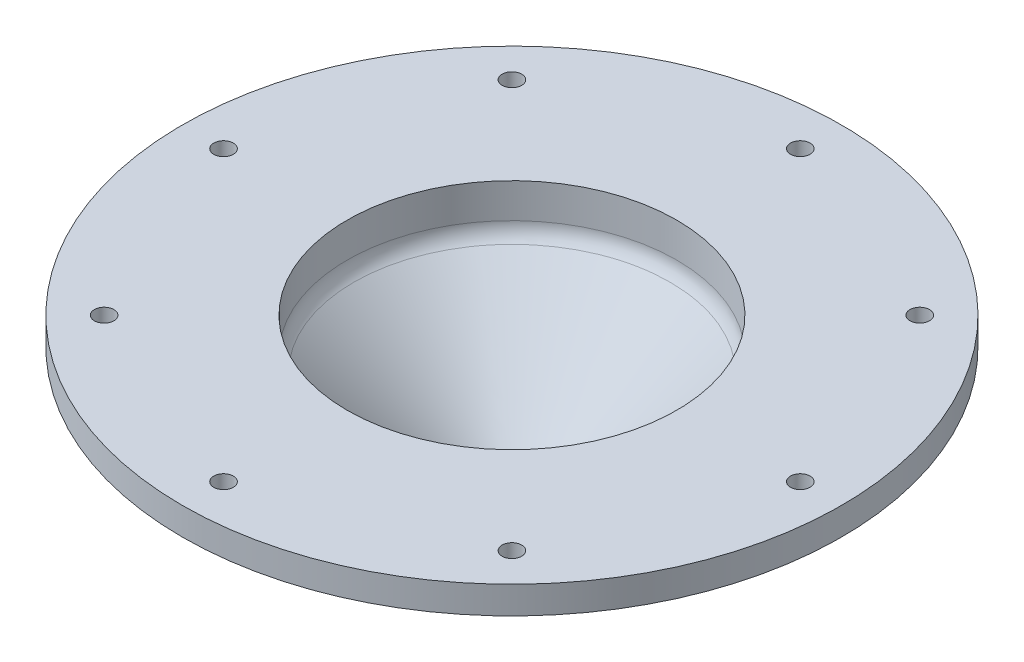
SolidWorks part; units mm, degrees
material "7075-T6 (SN)"
ref_plane "Front Plane" through (0, 0, 0) normal (0, 0, 1) x (1, 0, 0)
ref_plane "Top Plane" through (0, 0, 0) normal (0, 1, 0) x (1, 0, 0)
ref_plane "Right Plane" through (0, 0, 0) normal (1, 0, 0) x (0, 0, -1)
sketch "Sketch1" plane through (0, 0, 0) normal (0, 1, 0) x (1, 0, 0)
  circle A0 centre (0, 0) radius 38.1
  dimension "D1" = 76.2
extrude "Boss-Extrude1" add sketch "Sketch1" along normal blind 3.175
hole_wizard "Tap Drill for #4-40 Tap1" positions "Sketch3" profile "Sketch4" hole size "#4-40" standard "ANSI Inch" end condition through all
sketch "Sketch3" plane through (0, 0, 0) normal (0, -1, 0) x (-1, 0, 0)
  point P0 (0, -33.3375)
  dimension "D1" = 33.3375
sketch "Sketch4" plane through (0, 0, 33.3375) normal (1, 0, 0) x (0, 0, -1)
  line L0 (0, 0) -> (0, 3.175)
  line L1 (0, 3.175) -> (1.1303, 3.175)
  line L2 (1.1303, 3.175) -> (1.1303, 0)
  line L5 (1.1303, 0) -> (0, 0)
  line L11 (0, -6.35) -> (0, 107.95) construction
  dimension "Thru Hole Dia." = 2.2606
  dimension "Thru Hole Depth" = 3.175
pattern_circular "CirPattern1" count 8 over 360 about axis through (0, 0, 0) along (0, 1, 0) of "Tap Drill for #4-40 Tap1"
sketch "Sketch5" plane through (0, 0, 0) normal (0, -1, 0) x (1, 0, 0)
  circle A0 centre (0, 0) radius 25.4
  dimension "D1" = 50.8
extrude "Boss-Extrude2" add sketch "Sketch5" along normal blind 19.05
sketch "Sketch6" plane through (0, -19.05, 0) normal (0, -1, 0) x (1, 0, 0)
  circle A0 centre (0, 0) radius 4.7625
  dimension "D1" = 9.525
extrude "Cut-Extrude1" cut sketch "Sketch6" against normal through all both and the other way through all
sketch "Sketch7" plane through (0, 3.175, 0) normal (0, 1, 0) x (1, 0, 0)
  circle A0 centre (0, 0) radius 19.05
  dimension "D1" = 38.1
extrude "Cut-Extrude2" cut sketch "Sketch7" against normal blind 5.08
sketch "Sketch8" plane through (0, -1.905, 0) normal (0, 1, 0) x (1, 0, 0)
  circle A0 centre (0, 0) radius 19.05
  circle A1 centre (0, 0) radius 19.05 construction
  dimension "D1" = 0
ref_plane "Plane1" through (0, -15.875, 0) normal (0, -1, 0) x (-1, 0, 0)
sketch "Sketch9" plane through (0, -15.875, 0) normal (0, -1, 0) x (-1, 0, 0)
  circle A0 centre (0, 0) radius 4.7625
  circle A1 centre (0, 0) radius 4.7625 construction
  dimension "D1" = 0
loft "Cut-Loft1" cut profiles "Sketch8", "Sketch9" connector at (0, -1.905, 19.05) connector at (-1.301, -15.875, 4.5814)
chamfer "Chamfer1" distance 16.51 angle 45 1 edges at (0, -19.05, -25.4)
fillet "Fillet1" radius 2.54 1 edges at (0, 0, 25.4)
fillet "Fillet2" radius 2.54 1 edges at (0, -1.905, 19.05)
